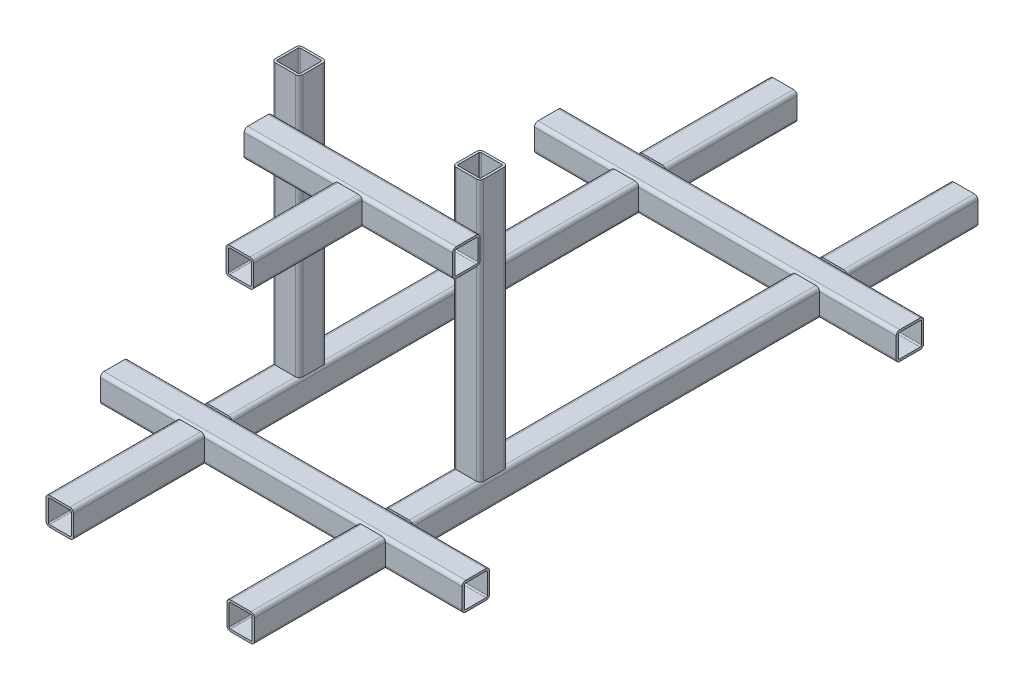
SolidWorks part; units mm, degrees
material "Alumina"
ref_plane "Front Plane" through (0, 0, 0) normal (0, 0, 1) x (1, 0, 0)
ref_plane "Top Plane" through (0, 0, 0) normal (0, 1, 0) x (1, 0, 0)
ref_plane "Right Plane" through (0, 0, 0) normal (1, 0, 0) x (0, 0, -1)
ref_plane "Bottom Face" through (0, 0, 0) normal (0, 1, 0) x (1, 0, 0)
ref_plane "Top Face" through (0, 38.1, 0) normal (0, 1, 0) x (1, 0, 0)
ref_plane "Mid Plane" through (0, 19.05, 0) normal (0, 1, 0) x (1, 0, 0)
ref_plane "Front Face" through (0, 0, 500) normal (0, 0, 1) x (1, 0, 0)
ref_plane "Back Face" through (0, 0, -500) normal (0, 0, 1) x (1, 0, 0)
ref_plane "Left Face" through (250, 0, 0) normal (1, 0, 0) x (0, 0, -1)
ref_plane "Right Face" through (-250, 0, 0) normal (1, 0, 0) x (0, 0, -1)
ref_plane "Divider Plane" through (0, 0, 150) normal (0, 0, 1) x (1, 0, 0)
ref_plane "Max Height Plane" through (0, 400, 0) normal (0, 1, 0) x (1, 0, 0)
ref_plane "Electronics Box Plane" through (0, 338.1, 0) normal (0, 1, 0) x (1, 0, 0)
sketch "Sketch2" plane through (250, 0, 0) normal (1, 0, 0) x (0, 0, -1)
  line L0 (330, 38.1) -> (-330, 38.1) construction
  line L5 (330, 0) -> (-330, 0) construction
  line L6 (0, 220) -> (0, -220) construction
  line L7 (-314.05, 38.1) -> (-285.95, 38.1)
  line L8 (-280.95, 33.1) -> (-280.95, 5)
  line L9 (-315.875, 33.1) -> (-315.875, 5)
  line L10 (-314.05, 3.175) -> (-285.95, 3.175)
  line L11 (-285.95, 0) -> (-314.05, 0)
  line L12 (-319.05, 5) -> (-319.05, 33.1)
  line L13 (-300, 38.1) -> (-300, 0) construction
  line L14 (-319.05, 19.05) -> (-280.95, 19.05) construction
  line L15 (-284.125, 5) -> (-284.125, 33.1)
  line L16 (-285.95, 34.925) -> (-314.05, 34.925)
  line L17 (-300, 34.925) -> (-300, 3.175) construction
  line L18 (-315.875, 19.05) -> (-284.125, 19.05) construction
  arc A0 (-285.95, 38.1) -> (-280.95, 33.1) centre (-285.95, 33.1) cw
  arc A1 (-280.95, 5) -> (-285.95, 0) centre (-285.95, 5) cw
  arc A2 (-314.05, 0) -> (-319.05, 5) centre (-314.05, 5) cw
  arc A3 (-319.05, 33.1) -> (-314.05, 38.1) centre (-314.05, 33.1) cw
  arc A4 (-315.875, 5) -> (-314.05, 3.175) centre (-314.05, 5) ccw
  arc A5 (-285.95, 3.175) -> (-284.125, 5) centre (-285.95, 5) ccw
  arc A6 (-284.125, 33.1) -> (-285.95, 34.925) centre (-285.95, 33.1) ccw
  arc A7 (-314.05, 34.925) -> (-315.875, 33.1) centre (-314.05, 33.1) ccw
  point P20 (-300, 19.05)
  point P39 (-300, 19.05)
  dimension "D1" = 5
  dimension "D2" = 300
  dimension "D3" = 3.175
extrude "Front Cross-Car Member" add sketch "Sketch2" against normal up to surface (500 mm away) up to plane "Right Face"
sketch "Sketch5" plane through (250, 0, 0) normal (1, 0, 0) x (0, 0, -1)
  line L0 (285.95, 38.1) -> (314.05, 38.1)
  line L1 (319.05, 33.1) -> (319.05, 5)
  line L2 (314.05, 0) -> (285.95, 0)
  line L3 (280.95, 5) -> (280.95, 33.1)
  line L4 (300, 38.1) -> (300, 0) construction
  line L5 (280.95, 19.05) -> (319.05, 19.05) construction
  line L6 (285.95, 34.925) -> (314.05, 34.925)
  line L7 (315.875, 33.1) -> (315.875, 5)
  line L8 (314.05, 3.175) -> (285.95, 3.175)
  line L9 (284.125, 5) -> (284.125, 33.1)
  line L10 (300, 34.925) -> (300, 3.175) construction
  line L11 (284.125, 19.05) -> (315.875, 19.05) construction
  line L12 (330, 0) -> (-330, 0) construction
  line L14 (330, 38.1) -> (-330, 38.1) construction
  line L15 (0, 220) -> (0, -220) construction
  arc A0 (314.05, 38.1) -> (319.05, 33.1) centre (314.05, 33.1) cw
  arc A1 (319.05, 5) -> (314.05, 0) centre (314.05, 5) cw
  arc A2 (285.95, 0) -> (280.95, 5) centre (285.95, 5) cw
  arc A3 (280.95, 33.1) -> (285.95, 38.1) centre (285.95, 33.1) cw
  arc A4 (314.05, 34.925) -> (315.875, 33.1) centre (314.05, 33.1) cw
  arc A5 (315.875, 5) -> (314.05, 3.175) centre (314.05, 5) cw
  arc A6 (285.95, 3.175) -> (284.125, 5) centre (285.95, 5) cw
  arc A7 (284.125, 33.1) -> (285.95, 34.925) centre (285.95, 33.1) cw
  point P32 (300, 19.05)
  point P33 (300, 19.05)
  dimension "D2" = 5
  dimension "D1" = 3.175
  dimension "D3" = 300
extrude "Back Cross-Car Member" add sketch "Sketch5" against normal up to surface (500 mm away) separate body up to plane "Right Face"
sketch "Sketch6" plane through (0, 0, -500) normal (0, 0, 1) x (1, 0, 0)
  line L0 (110.95, 38.1) -> (139.05, 38.1)
  line L1 (144.05, 33.1) -> (144.05, 5)
  line L2 (109.125, 33.1) -> (109.125, 5)
  line L3 (110.95, 3.175) -> (139.05, 3.175)
  line L4 (139.05, 0) -> (110.95, 0)
  line L5 (105.95, 5) -> (105.95, 33.1)
  line L6 (125, 38.1) -> (125, 0) construction
  line L7 (105.95, 19.05) -> (144.05, 19.05) construction
  line L8 (140.875, 5) -> (140.875, 33.1)
  line L9 (139.05, 34.925) -> (110.95, 34.925)
  line L10 (125, 34.925) -> (125, 3.175) construction
  line L11 (109.125, 19.05) -> (140.875, 19.05) construction
  line L12 (330, 38.1) -> (-330, 38.1) construction
  line L13 (330, 0) -> (-330, 0) construction
  line L14 (0, -220) -> (0, 220) construction
  arc A0 (139.05, 38.1) -> (144.05, 33.1) centre (139.05, 33.1) cw
  arc A1 (144.05, 5) -> (139.05, 0) centre (139.05, 5) cw
  arc A2 (110.95, 0) -> (105.95, 5) centre (110.95, 5) cw
  arc A3 (105.95, 33.1) -> (110.95, 38.1) centre (110.95, 33.1) cw
  arc A4 (109.125, 5) -> (110.95, 3.175) centre (110.95, 5) ccw
  arc A5 (139.05, 3.175) -> (140.875, 5) centre (139.05, 5) ccw
  arc A6 (140.875, 33.1) -> (139.05, 34.925) centre (139.05, 33.1) ccw
  arc A7 (110.95, 34.925) -> (109.125, 33.1) centre (110.95, 33.1) ccw
  point P16 (125, 19.05)
  point P33 (125, 19.05)
  dimension "D1" = 5
  dimension "D2" = 3.175
  dimension "D3" = 125
extrude "Back Left Along-Car Member" add sketch "Sketch6" along normal blind 180.95
extrude "Middle Left Along-Car Member" add sketch "Sketch6<2>" along normal blind 561.9 from offset 219.05
sketch "Sketch6<2>" plane through (0, 0, -500) normal (0, 0, 1) x (1, 0, 0) same geometry as "Sketch6"
extrude "Front Left Along-Car Member" add sketch "Sketch6<3>" along normal blind 180.95 from offset 819.05
sketch "Sketch6<3>" plane through (0, 0, -500) normal (0, 0, 1) x (1, 0, 0) same geometry as "Sketch6"
sketch "Sketch7" plane through (0, 0, -500) normal (0, 0, 1) x (1, 0, 0)
  line L0 (-139.05, 38.1) -> (-110.95, 38.1)
  line L1 (-105.95, 33.1) -> (-105.95, 5)
  line L2 (-140.875, 33.1) -> (-140.875, 5)
  line L3 (-139.05, 3.175) -> (-110.95, 3.175)
  line L4 (-110.95, 0) -> (-139.05, 0)
  line L5 (-144.05, 5) -> (-144.05, 33.1)
  line L6 (-125, 38.1) -> (-125, 0) construction
  line L7 (-144.05, 19.05) -> (-105.95, 19.05) construction
  line L8 (-109.125, 5) -> (-109.125, 33.1)
  line L9 (-110.95, 34.925) -> (-139.05, 34.925)
  line L10 (-125, 34.925) -> (-125, 3.175) construction
  line L11 (-140.875, 19.05) -> (-109.125, 19.05) construction
  line L12 (330, 38.1) -> (-330, 38.1) construction
  line L13 (330, 0) -> (-330, 0) construction
  line L14 (0, -220) -> (0, 220) construction
  arc A0 (-110.95, 38.1) -> (-105.95, 33.1) centre (-110.95, 33.1) cw
  arc A1 (-105.95, 5) -> (-110.95, 0) centre (-110.95, 5) cw
  arc A2 (-139.05, 0) -> (-144.05, 5) centre (-139.05, 5) cw
  arc A3 (-144.05, 33.1) -> (-139.05, 38.1) centre (-139.05, 33.1) cw
  arc A4 (-140.875, 5) -> (-139.05, 3.175) centre (-139.05, 5) ccw
  arc A5 (-110.95, 3.175) -> (-109.125, 5) centre (-110.95, 5) ccw
  arc A6 (-109.125, 33.1) -> (-110.95, 34.925) centre (-110.95, 33.1) ccw
  arc A7 (-139.05, 34.925) -> (-140.875, 33.1) centre (-139.05, 33.1) ccw
  point P16 (-125, 19.05)
  point P33 (-125, 19.05)
  dimension "D1" = 5
  dimension "D2" = 3.175
  dimension "D3" = 125
extrude "Back Right Along-Car Member" add sketch "Sketch7" along normal blind 180.95
extrude "Middle Right Along-Car Member" add sketch "Sketch7<2>" along normal blind 561.9 from offset 219.05
sketch "Sketch7<2>" plane through (0, 0, -500) normal (0, 0, 1) x (1, 0, 0) same geometry as "Sketch7"
extrude "Front Right Along-Car Member" add sketch "Sketch7<3>" along normal blind 180.95 from offset 819.05
sketch "Sketch7<3>" plane through (0, 0, -500) normal (0, 0, 1) x (1, 0, 0) same geometry as "Sketch7"
sketch "Sketch8" plane through (0, 38.1, 0) normal (0, 1, 0) x (1, 0, 0)
  line L0 (-139.05, -150) -> (-110.95, -150)
  line L1 (-105.95, -155) -> (-105.95, -183.1)
  line L2 (-140.875, -155) -> (-140.875, -183.1)
  line L3 (-139.05, -184.925) -> (-110.95, -184.925)
  line L4 (-110.95, -188.1) -> (-139.05, -188.1)
  line L5 (-144.05, -183.1) -> (-144.05, -155)
  line L6 (-125, -150) -> (-125, -188.1) construction
  line L7 (-144.05, -169.05) -> (-105.95, -169.05) construction
  line L8 (-109.125, -183.1) -> (-109.125, -155)
  line L9 (-110.95, -153.175) -> (-139.05, -153.175)
  line L10 (-125, -153.175) -> (-125, -184.925) construction
  line L11 (-140.875, -169.05) -> (-109.125, -169.05) construction
  line L12 (-220, -150) -> (220, -150) construction
  line L13 (0, -220) -> (0, 220) construction
  arc A0 (-110.95, -150) -> (-105.95, -155) centre (-110.95, -155) cw
  arc A1 (-105.95, -183.1) -> (-110.95, -188.1) centre (-110.95, -183.1) cw
  arc A2 (-139.05, -188.1) -> (-144.05, -183.1) centre (-139.05, -183.1) cw
  arc A3 (-144.05, -155) -> (-139.05, -150) centre (-139.05, -155) cw
  arc A4 (-140.875, -183.1) -> (-139.05, -184.925) centre (-139.05, -183.1) ccw
  arc A5 (-110.95, -184.925) -> (-109.125, -183.1) centre (-110.95, -183.1) ccw
  arc A6 (-109.125, -155) -> (-110.95, -153.175) centre (-110.95, -155) ccw
  arc A7 (-139.05, -153.175) -> (-140.875, -155) centre (-139.05, -155) ccw
  point P16 (-125, -169.05)
  point P33 (-125, -169.05)
  dimension "D1" = 5
  dimension "D2" = 3.175
  dimension "D3" = 38.1
  dimension "D4" = 125
extrude "Right Vertical Member" add sketch "Sketch8" along normal up to surface (361.9 mm away) up to plane "Max Height Plane"
sketch "Sketch10" plane through (0, 38.1, 0) normal (0, 1, 0) x (1, 0, 0)
  line L0 (110.95, -150) -> (139.05, -150)
  line L1 (144.05, -155) -> (144.05, -183.1)
  line L2 (109.125, -155) -> (109.125, -183.1)
  line L3 (110.95, -184.925) -> (139.05, -184.925)
  line L4 (139.05, -188.1) -> (110.95, -188.1)
  line L5 (105.95, -183.1) -> (105.95, -155)
  line L6 (125, -150) -> (125, -188.1) construction
  line L7 (105.95, -169.05) -> (144.05, -169.05) construction
  line L8 (140.875, -183.1) -> (140.875, -155)
  line L9 (139.05, -153.175) -> (110.95, -153.175)
  line L10 (125, -153.175) -> (125, -184.925) construction
  line L11 (109.125, -169.05) -> (140.875, -169.05) construction
  line L12 (-220, -150) -> (220, -150) construction
  line L13 (0, -220) -> (0, 220) construction
  arc A0 (139.05, -150) -> (144.05, -155) centre (139.05, -155) cw
  arc A1 (144.05, -183.1) -> (139.05, -188.1) centre (139.05, -183.1) cw
  arc A2 (110.95, -188.1) -> (105.95, -183.1) centre (110.95, -183.1) cw
  arc A3 (105.95, -155) -> (110.95, -150) centre (110.95, -155) cw
  arc A4 (109.125, -183.1) -> (110.95, -184.925) centre (110.95, -183.1) ccw
  arc A5 (139.05, -184.925) -> (140.875, -183.1) centre (139.05, -183.1) ccw
  arc A6 (140.875, -155) -> (139.05, -153.175) centre (139.05, -155) ccw
  arc A7 (110.95, -153.175) -> (109.125, -155) centre (110.95, -155) ccw
  point P16 (125, -169.05)
  point P33 (125, -169.05)
  dimension "D1" = 5
  dimension "D2" = 3.175
  dimension "D3" = 38.1
  dimension "D4" = 125
extrude "Left Vertical Member" add sketch "Sketch10" along normal up to surface (361.9 mm away) up to plane "Max Height Plane"
sketch "Sketch11" plane through (250, 0, 0) normal (1, 0, 0) x (0, 0, -1)
  line L0 (-221.2, 338.1) -> (-193.1, 338.1)
  line L1 (-188.1, 333.1) -> (-188.1, 305)
  line L2 (-223.025, 333.1) -> (-223.025, 305)
  line L3 (-221.2, 303.175) -> (-193.1, 303.175)
  line L4 (-193.1, 300) -> (-221.2, 300)
  line L5 (-226.2, 305) -> (-226.2, 333.1)
  line L6 (-207.15, 338.1) -> (-207.15, 300) construction
  line L7 (-226.2, 319.05) -> (-188.1, 319.05) construction
  line L8 (-191.275, 305) -> (-191.275, 333.1)
  line L9 (-193.1, 334.925) -> (-221.2, 334.925)
  line L10 (-207.15, 334.925) -> (-207.15, 303.175) construction
  line L11 (-223.025, 319.05) -> (-191.275, 319.05) construction
  line L12 (-150, 220) -> (-150, -220) construction
  line L13 (330, 338.1) -> (-330, 338.1) construction
  arc A0 (-193.1, 338.1) -> (-188.1, 333.1) centre (-193.1, 333.1) cw
  arc A1 (-188.1, 305) -> (-193.1, 300) centre (-193.1, 305) cw
  arc A2 (-221.2, 300) -> (-226.2, 305) centre (-221.2, 305) cw
  arc A3 (-226.2, 333.1) -> (-221.2, 338.1) centre (-221.2, 333.1) cw
  arc A4 (-223.025, 305) -> (-221.2, 303.175) centre (-221.2, 305) ccw
  arc A5 (-193.1, 303.175) -> (-191.275, 305) centre (-193.1, 305) ccw
  arc A6 (-191.275, 333.1) -> (-193.1, 334.925) centre (-193.1, 333.1) ccw
  arc A7 (-221.2, 334.925) -> (-223.025, 333.1) centre (-221.2, 333.1) ccw
  point P16 (-207.15, 319.05)
  point P33 (-207.15, 319.05)
  dimension "D1" = 5
  dimension "D2" = 3.175
  dimension "D3" = 38.1
  dimension "D4" = 38.1
extrude "Upper Cross-Car Member" add sketch "Sketch11" against normal blind 288.1 from offset 105.95 offset against normal yes
sketch "Sketch12" plane through (0, 0, 150) normal (0, 0, 1) x (1, 0, 0)
  line L0 (-14.05, 338.1) -> (14.05, 338.1)
  line L1 (19.05, 333.1) -> (19.05, 305)
  line L2 (-15.875, 333.1) -> (-15.875, 305)
  line L3 (-14.05, 303.175) -> (14.05, 303.175)
  line L4 (14.05, 300) -> (-14.05, 300)
  line L5 (-19.05, 305) -> (-19.05, 333.1)
  line L6 (0, 338.1) -> (0, 300) construction
  line L7 (-19.05, 319.05) -> (19.05, 319.05) construction
  line L8 (15.875, 305) -> (15.875, 333.1)
  line L9 (14.05, 334.925) -> (-14.05, 334.925)
  line L10 (0, 334.925) -> (0, 303.175) construction
  line L11 (-15.875, 319.05) -> (15.875, 319.05) construction
  line L12 (330, 338.1) -> (-330, 338.1) construction
  line L13 (0, -220) -> (0, 220) construction
  arc A0 (14.05, 338.1) -> (19.05, 333.1) centre (14.05, 333.1) cw
  arc A1 (19.05, 305) -> (14.05, 300) centre (14.05, 305) cw
  arc A2 (-14.05, 300) -> (-19.05, 305) centre (-14.05, 305) cw
  arc A3 (-19.05, 333.1) -> (-14.05, 338.1) centre (-14.05, 333.1) cw
  arc A4 (-15.875, 305) -> (-14.05, 303.175) centre (-14.05, 305) ccw
  arc A5 (14.05, 303.175) -> (15.875, 305) centre (14.05, 305) ccw
  arc A6 (15.875, 333.1) -> (14.05, 334.925) centre (14.05, 333.1) ccw
  arc A7 (-14.05, 334.925) -> (-15.875, 333.1) centre (-14.05, 333.1) ccw
  point P16 (0, 319.05)
  point P33 (0, 319.05)
  dimension "D1" = 5
  dimension "D2" = 3.175
  dimension "D3" = 38.1
extrude "E-Box Platform Base" add sketch "Sketch12" along normal blind 150 from offset 76.2
equation "\"D1@Front Face\" = \"frameLength@Master Assembly.SLDASM\" / 2"
equation "\"D1@Back Face\" = \"frameLength@Master Assembly.SLDASM\" / 2"
equation "\"D1@Left Face\"=\"frameWidth@Master Assembly.SLDASM\"/2"
equation "\"D1@Right Face\" = \"frameWidth@Master Assembly.SLDASM\" / 2"
equation "\"D1@Top Face\"=\"frameTubeStockHeight@Master Assembly.SLDASM\""
equation "\"D2@Sketch2\"=\"frameMemberDistLength@Master Assembly.SLDASM\"/2"
equation "\"D3@Sketch2\"=\"frameTubeStockWallThickness@Master Assembly.SLDASM\""
equation "\"D1@Sketch5\"=\"frameTubeStockWallThickness@Master Assembly.SLDASM\""
equation "\"D3@Sketch5\"=\"frameMemberDistLength@Master Assembly.SLDASM\"/2"
equation "\"D3@Sketch6\"=\"frameMemberDistWidth@Master Assembly.SLDASM\"/2"
equation "\"D1@Back Left Along-Car Member\"=(\"frameLength@Master Assembly.SLDASM\" - \"frameMemberDistLength@Master Assembly.SLDASM\" - \"frameTubeStockHeight@Master Assembly.SLDASM\")  / 2"
equation "\"D19@Middle Left Along-Car Member\" = ( \"frameLength@Master Assembly.SLDASM\" - \"frameMemberDistLength@Master Assembly.SLDASM\" + \"frameTubeStockHeight@Master Assembly.SLDASM\" ) / 2"
equation "\"D1@Middle Left Along-Car Member\"=\"frameMemberDistLength@Master Assembly.SLDASM\" - \"frameTubeStockHeight@Master Assembly.SLDASM\""
equation "\"D19@Front Left Along-Car Member\"=( \"frameLength@Master Assembly.SLDASM\" - \"frameMemberDistLength@Master Assembly.SLDASM\" )  / 2 + \"frameMemberDistLength@Master Assembly.SLDASM\" + \"frameTubeStockHeight@Master Assembly.SLDASM\" / 2"
equation "\"D1@Front Left Along-Car Member\"=(\"frameLength@Master Assembly.SLDASM\" - \"frameMemberDistLength@Master Assembly.SLDASM\" - \"frameTubeStockHeight@Master Assembly.SLDASM\")  / 2"
equation "\"D3@Sketch7\"=\"frameMemberDistWidth@Master Assembly.SLDASM\"/2"
equation "\"D1@Back Right Along-Car Member\"=(\"frameLength@Master Assembly.SLDASM\" - \"frameMemberDistLength@Master Assembly.SLDASM\" - \"frameTubeStockHeight@Master Assembly.SLDASM\")  / 2"
equation "\"D19@Middle Right Along-Car Member\" = ( \"frameLength@Master Assembly.SLDASM\" - \"frameMemberDistLength@Master Assembly.SLDASM\" + \"frameTubeStockHeight@Master Assembly.SLDASM\" ) / 2"
equation "\"D1@Middle Right Along-Car Member\"=\"frameMemberDistLength@Master Assembly.SLDASM\" - \"frameTubeStockHeight@Master Assembly.SLDASM\""
equation "\"D19@Front Right Along-Car Member\"=( \"frameLength@Master Assembly.SLDASM\" - \"frameMemberDistLength@Master Assembly.SLDASM\" )  / 2 + \"frameMemberDistLength@Master Assembly.SLDASM\" + \"frameTubeStockHeight@Master Assembly.SLDASM\" / 2"
equation "\"D1@Front Right Along-Car Member\"=(\"frameLength@Master Assembly.SLDASM\" - \"frameMemberDistLength@Master Assembly.SLDASM\" - \"frameTubeStockHeight@Master Assembly.SLDASM\")  / 2"
equation "\"D1@Divider Plane\"= \"frameDividerPlaneOffset@Master Assembly.SLDASM\""
equation "\"D3@Sketch8\"=\"frameTubeStockHeight@Master Assembly.SLDASM\""
equation "\"D4@Sketch8\"=\"frameMemberDistWidth@Master Assembly.SLDASM\"/2"
equation "\"D1@Max Height Plane\" = \"frameHeight@Master Assembly.SLDASM\""
equation "\"D4@Sketch10\"=\"frameMemberDistWidth@Master Assembly.SLDASM\"/2"
equation "\"D1@Electronics Box Plane\" = \"eboxPlaneHeight@Master Assembly.SLDASM\""
equation "\"D4@Sketch11\"=\"frameTubeStockHeight@Master Assembly.SLDASM\""
equation "\"D19@Upper Cross-Car Member\" = ( \"frameWidth@Master Assembly.SLDASM\" - \"frameMemberDistWidth@Master Assembly.SLDASM\" - \"frameTubeStockHeight@Master Assembly.SLDASM\" ) / 2"
equation "\"D1@Upper Cross-Car Member\" = \"frameMemberDistWidth@Master Assembly.SLDASM\" + \"frameTubeStockHeight@Master Assembly.SLDASM\""
equation "\"D19@E-Box Platform Base\"= \"frameTubeStockHeight@Master Assembly.SLDASM\" * 2"
equation "\"D2@Sketch6\"=\"frameTubeStockWallThickness@Master Assembly.SLDASM\""
equation "\"D2@Sketch7\"=\"frameTubeStockWallThickness@Master Assembly.SLDASM\""
equation "\"D2@Sketch8\"=\"frameTubeStockWallThickness@Master Assembly.SLDASM\""
equation "\"D3@Sketch10\"=\"frameTubeStockHeight@Master Assembly.SLDASM\""
equation "\"D2@Sketch10\"=\"frameTubeStockWallThickness@Master Assembly.SLDASM\""
equation "\"D3@Sketch11\"=\"frameTubeStockHeight@Master Assembly.SLDASM\""
equation "\"D2@Sketch11\"=\"frameTubeStockWallThickness@Master Assembly.SLDASM\""
equation "\"D3@Sketch12\"=\"frameTubeStockHeight@Master Assembly.SLDASM\""
equation "\"D2@Sketch12\"=\"frameTubeStockWallThickness@Master Assembly.SLDASM\""
